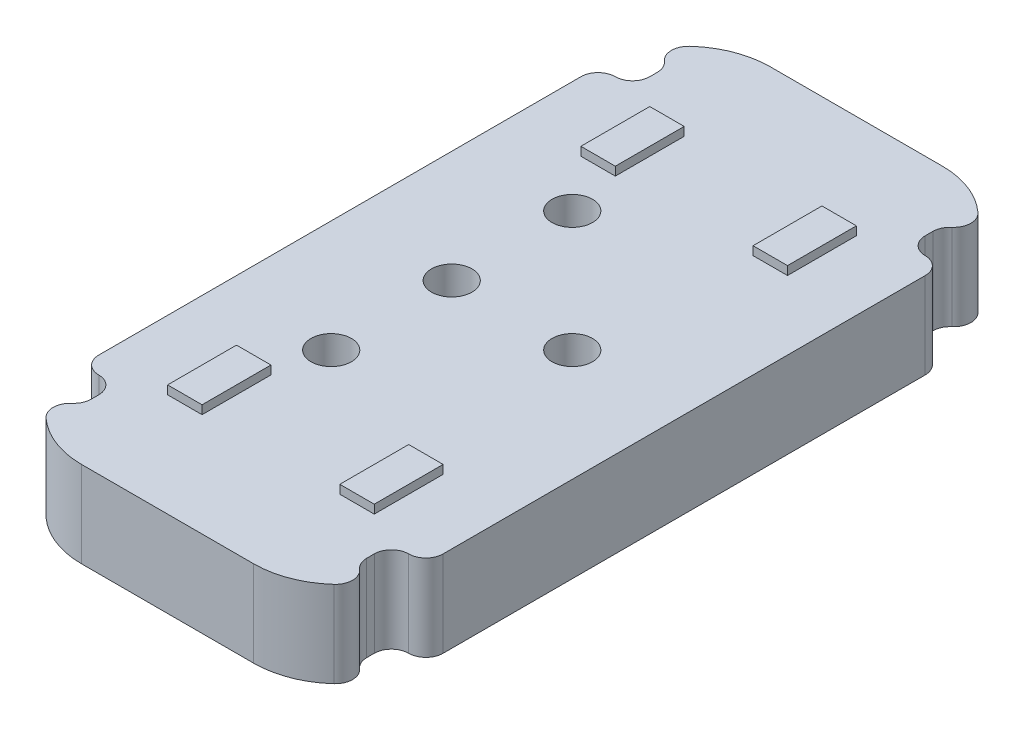
SolidWorks part; units mm, degrees
ref_plane "Front Plane" through (0, 0, 0) normal (0, 0, 1) x (1, 0, 0)
ref_plane "Top Plane" through (0, 0, 0) normal (0, 1, 0) x (1, 0, 0)
ref_plane "Right Plane" through (0, 0, 0) normal (1, 0, 0) x (0, 0, -1)
sketch "Sketch1" plane through (0, 0, 0) normal (0, 1, 0) x (1, 0, 0)
  line L0 (0, 0) -> (0, 7) construction
  line L1 (0, 0) -> (0, -7) construction
  line L2 (0, 0) -> (7, 0) construction
  line L3 (3.5, 2.1389) -> (3.5, -2.1389) construction
  line L4 (-6.5, 20) -> (13.5, 20)
  line L5 (-6.5, 20) -> (-6.5, -20)
  line L6 (-6.5, -20) -> (13.5, -20)
  line L7 (13.5, 20) -> (13.5, -20)
  circle A0 centre (0, 0) radius 1.175
  circle A1 centre (0, 7) radius 1.175
  circle A2 centre (7, 0) radius 1.175
  circle A3 centre (0, -7) radius 1.175
  point P13 (13.5, 0)
  point P16 (3.5, 0)
  point P17 (3.5, -20)
  dimension "D1" = 2.35
  dimension "D2" = 7
  dimension "D3" = 20
  dimension "D4" = 40
extrude "Boss-Extrude1" add sketch "Sketch1" along normal blind 5
fillet "Fillet1" radius 5 4 edges at (-6.5, 2.5, 20) (13.5, 2.5, 20) (13.5, 2.5, -20) (-6.5, 2.5, -20)
sketch "Sketch2" plane through (0, 5, 0) normal (0, 1, 0) x (1, 0, 0)
  line L0 (3.5, 20) -> (3.5, -20) construction
  line L1 (-2.5, 14) -> (-0.5, 14)
  line L2 (-2.5, 14) -> (-2.5, 10)
  line L3 (-2.5, 10) -> (-0.5, 10)
  line L4 (-0.5, 14) -> (-0.5, 10)
  line L5 (8.5, 20) -> (-1.5, 20) construction
  line L6 (-1.5, -20) -> (8.5, -20) construction
  line L7 (-6.5, 0) -> (13.5, 0) construction
  line L8 (-6.5, 15) -> (-6.5, -15) construction
  line L9 (13.5, -15) -> (13.5, 15) construction
  dimension "D1" = 10
  dimension "D2" = 4
  dimension "D3" = 2
  dimension "D4" = 4
extrude "Boss-Extrude2" add sketch "Sketch2" along normal blind 0.5
pattern_linear "LPattern1" count 2 spacing 10 along (1, 0, 0) count 2 spacing 24 along (0, 0, 1) of "Boss-Extrude2"
sketch "Sketch3" plane through (0, 0, 20) normal (0, 0, 1) x (1, 0, 0)
  line L0 (-6.5, 5) -> (13.5, 5) construction
  circle A0 centre (3.5, 21.25) radius 16.25
  point P6 (3.5, 5)
  dimension "D1" = 32.5
sketch "Sketch4" plane through (0, 0, 0) normal (0, -1, 0) x (1, 0, 0)
  line L0 (3.5, 20) -> (3.5, -20) construction
  line L1 (-7.5496, 17.4404) -> (-5.5, 17.4404)
  line L2 (-7.5496, 17.4404) -> (-7.5496, 15)
  line L3 (-7.5496, 15) -> (-5.5, 15)
  line L4 (-4.5, 16.4404) -> (-4.5, 16)
  line L5 (-1.5, 20) -> (8.5, 20) construction
  line L6 (8.5, -20) -> (-1.5, -20) construction
  line L7 (-6.5, 0) -> (13.5, 0) construction
  line L8 (-6.5, -15) -> (-6.5, 15) construction
  line L9 (13.5, 15) -> (13.5, -15) construction
  line L10 (14.5496, 17.4404) -> (14.5496, 15)
  line L11 (14.5496, 15) -> (12.5, 15)
  line L12 (11.5, 16.4404) -> (11.5, 16)
  line L13 (14.5496, 17.4404) -> (12.5, 17.4404)
  line L14 (14.5496, -17.4404) -> (12.5, -17.4404)
  line L15 (11.5, -16.4404) -> (11.5, -16)
  line L16 (14.5496, -15) -> (12.5, -15)
  line L17 (14.5496, -17.4404) -> (14.5496, -15)
  line L18 (-4.5, -16.4404) -> (-4.5, -16)
  line L19 (-7.5496, -15) -> (-5.5, -15)
  line L20 (-7.5496, -17.4404) -> (-7.5496, -15)
  line L21 (-7.5496, -17.4404) -> (-5.5, -17.4404)
  arc A0 (-5.5, 15) -> (-4.5, 16) centre (-5.5, 16) ccw
  arc A1 (-5.5, 17.4404) -> (-4.5, 16.4404) centre (-5.5, 16.4404) cw
  arc A2 (12.5, 15) -> (11.5, 16) centre (12.5, 16) cw
  arc A3 (12.5, 17.4404) -> (11.5, 16.4404) centre (12.5, 16.4404) ccw
  arc A4 (12.5, -17.4404) -> (11.5, -16.4404) centre (12.5, -16.4404) cw
  arc A5 (12.5, -15) -> (11.5, -16) centre (12.5, -16) ccw
  arc A6 (-5.5, -17.4404) -> (-4.5, -16.4404) centre (-5.5, -16.4404) ccw
  arc A7 (-5.5, -15) -> (-4.5, -16) centre (-5.5, -16) cw
  dimension "D3" = 1
  dimension "D1" = 15
  dimension "D2" = 2
extrude "Cut-Extrude1" cut sketch "Sketch4" against normal through all
fillet "Fillet2" radius 1 8 edges at (12.864, 2.5, -17.4404) (13.5, 2.5, -15) (-5.864, 2.5, -17.4404) (-6.5, 2.5, -15) (13.5, 2.5, 15) (12.864, 2.5, 17.4404) (-6.5, 2.5, 15) (-5.864, 2.5, 17.4404)
